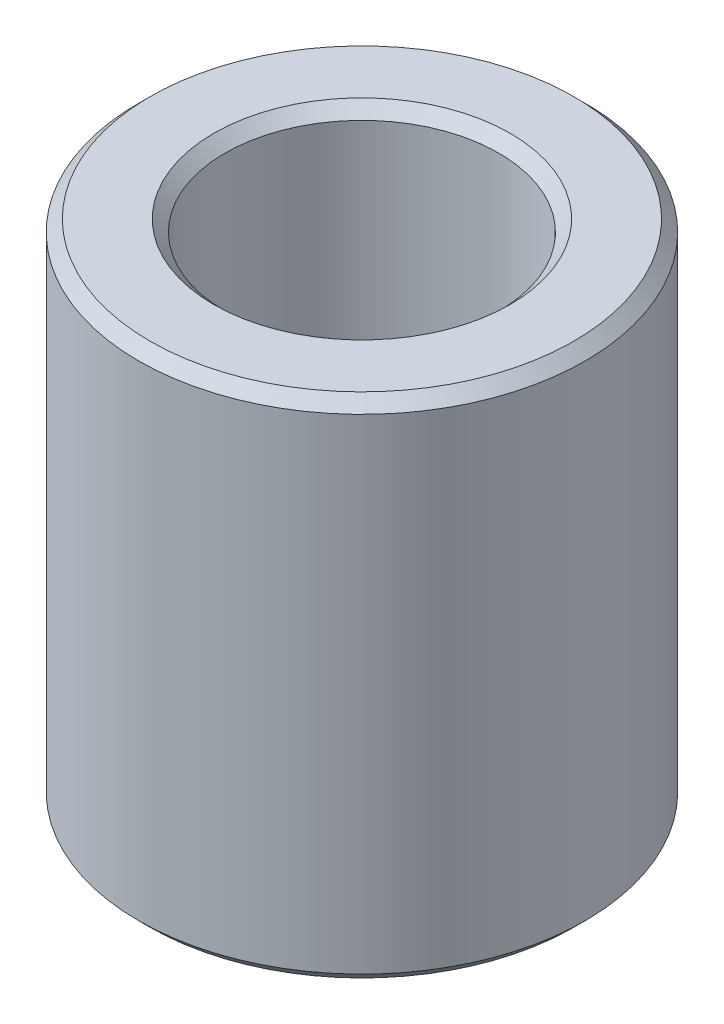
SolidWorks part; units mm, degrees
ref_plane "Front Plane" through (0, 0, 0) normal (0, 0, 1) x (1, 0, 0)
ref_plane "Top Plane" through (0, 0, 0) normal (0, 1, 0) x (1, 0, 0)
ref_plane "Right Plane" through (0, 0, 0) normal (1, 0, 0) x (0, 0, -1)
sketch "Sketch1" plane through (0, 0, 0) normal (0, 1, 0) x (1, 0, 0)
  circle A0 centre (0, 0) radius 20
  dimension "SLEEVE_OD" = 40
extrude "Boss-Extrude1" add sketch "Sketch1" along normal blind 45.4694
sketch "Sketch2" plane through (0, 0, 0) normal (0, 1, 0) x (1, 0, 0)
  circle A0 centre (0, 0) radius 12.2599
  dimension "BORE_D" = 24.5198
extrude "Cut-Extrude1" cut sketch "Sketch2" along normal through all
chamfer "Chamfer1" distance 1.0224 angle 45 4 edges at (0, 45.4694, 12.2599) (0, 0, 12.2599) (0, 0, 20) (0, 45.4694, 20)
